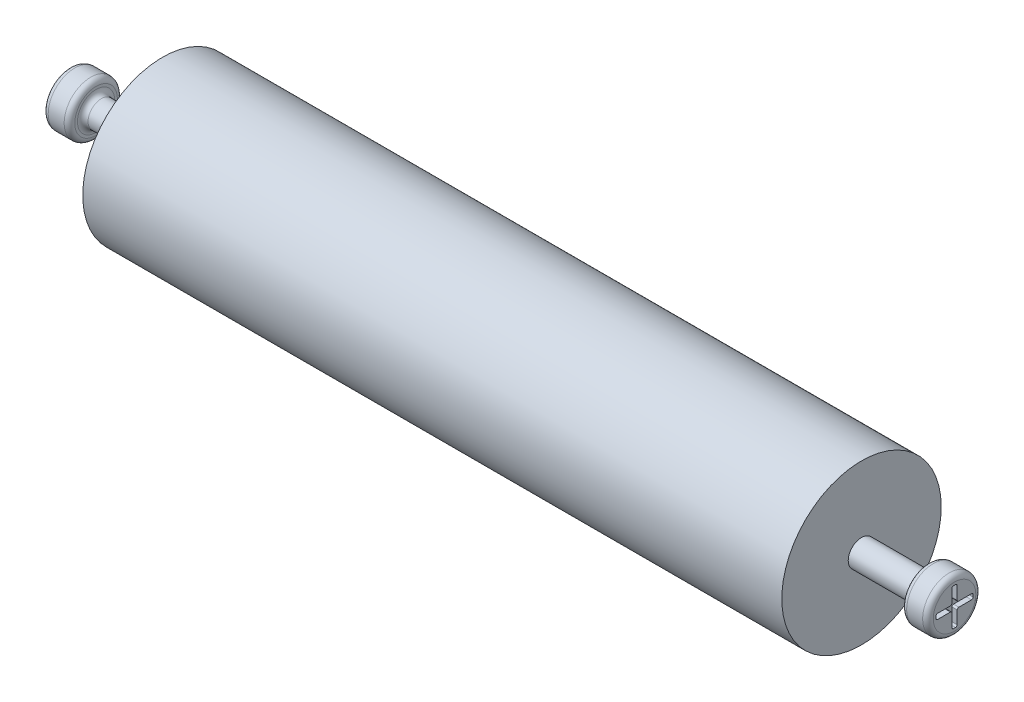
SolidWorks part; units mm, degrees
ref_plane "Front Plane" through (0, 0, 0) normal (0, 0, 1) x (1, 0, 0)
ref_plane "Top Plane" through (0, 0, 0) normal (0, 1, 0) x (1, 0, 0)
ref_plane "Right Plane" through (0, 0, 0) normal (1, 0, 0) x (0, 0, -1)
sketch "Sketch1" plane through (0, 0, 0) normal (1, 0, 0) x (0, 0, -1)
  circle A0 centre (0, 0) radius 38.1
extrude "Boss-Extrude1" add sketch "Sketch1" along normal blind 167.005 and the other way blind 167.005
sketch "Sketch2" plane through (-167.005, 0, 0) normal (-1, 0, 0) x (0, 0, 1)
  circle A0 centre (0, 0) radius 6.35
extrude "Boss-Extrude2" add sketch "Sketch2" along normal blind 31.75
sketch "Sketch3" plane through (-198.755, 0, 0) normal (-1, 0, 0) x (0, 0, 1)
  circle A0 centre (0, 0) radius 12.7
extrude "Boss-Extrude3" add sketch "Sketch3" along normal blind 12.7
fillet "Fillet1" radius 2.54 3 edges at (-198.755, 0, 6.35) (-198.755, 0, 12.7) (-211.455, 0, 12.7)
sketch "Sketch5" plane through (-211.455, 0, 0) normal (-1, 0, 0) x (0, 0, 1)
  line L1 (-0.508, 8.89) -> (0.508, 8.89)
  line L2 (-1.27, 8.128) -> (-1.27, 2.032)
  line L3 (-0.508, -8.89) -> (0.508, -8.89)
  line L4 (1.27, 8.128) -> (1.27, 2.032)
  line L7 (-8.128, 1.27) -> (-2.032, 1.27)
  line L8 (-8.89, 0.508) -> (-8.89, -0.508)
  line L9 (-8.128, -1.27) -> (-2.032, -1.27)
  line L10 (8.89, 0.508) -> (8.89, -0.508)
  line L16 (1.27, -2.032) -> (1.27, -8.128)
  line L17 (-1.27, -2.032) -> (-1.27, -8.128)
  line L18 (2.032, -1.27) -> (8.128, -1.27)
  line L19 (2.032, 1.27) -> (8.128, 1.27)
  arc A0 (-8.89, -0.508) -> (-8.128, -1.27) centre (-8.128, -0.508) ccw
  arc A1 (-1.27, -2.032) -> (-2.032, -1.27) centre (-2.032, -2.032) ccw
  arc A2 (1.27, -2.032) -> (2.032, -1.27) centre (2.032, -2.032) cw
  arc A3 (-0.508, -8.89) -> (-1.27, -8.128) centre (-0.508, -8.128) cw
  arc A4 (0.508, -8.89) -> (1.27, -8.128) centre (0.508, -8.128) ccw
  arc A5 (8.89, 0.508) -> (8.128, 1.27) centre (8.128, 0.508) ccw
  arc A6 (8.89, -0.508) -> (8.128, -1.27) centre (8.128, -0.508) cw
  arc A7 (-1.27, 8.128) -> (-0.508, 8.89) centre (-0.508, 8.128) cw
  arc A8 (-8.89, 0.508) -> (-8.128, 1.27) centre (-8.128, 0.508) cw
  arc A9 (1.27, 8.128) -> (0.508, 8.89) centre (0.508, 8.128) ccw
  arc A10 (2.032, 1.27) -> (1.27, 2.032) centre (2.032, 2.032) cw
  arc A11 (-1.27, 2.032) -> (-2.032, 1.27) centre (-2.032, 2.032) cw
  point P0 (0, 0)
  point P6 (0, 0)
  point P37 (1.27, 1.27)
  dimension "D1" = 0.762
  dimension "D2" = 0.762
  dimension "D3" = 0.762
extrude "Cut-Extrude1" cut sketch "Sketch5" against normal blind 2.54
mirror "Mirror1" about plane through (0, 0, 0) normal (1, 0, 0) of "Fillet1", "Boss-Extrude2", "Boss-Extrude3", "Cut-Extrude1"
